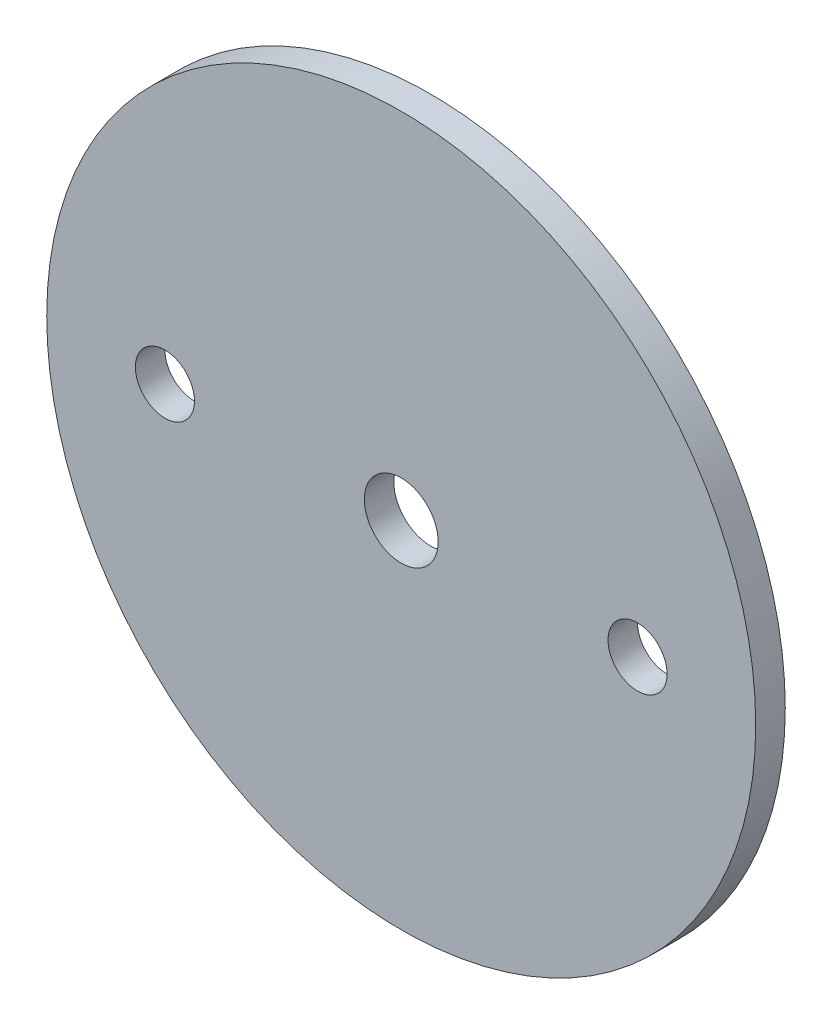
SolidWorks part; units mm, degrees
ref_plane "Front Plane" through (0, 0, 0) normal (0, 0, 1) x (1, 0, 0)
ref_plane "Top Plane" through (0, 0, 0) normal (0, 1, 0) x (1, 0, 0)
ref_plane "Right Plane" through (0, 0, 0) normal (1, 0, 0) x (0, 0, -1)
sketch "Sketch1" plane through (0, 0, 0) normal (0, 0, 1) x (1, 0, 0)
  circle A0 centre (0, 0) radius 38.1
extrude "Boss-Extrude1" add sketch "Sketch1" along normal mid plane 3.175
sketch "Sketch2" plane through (0, 0, 1.5875) normal (0, 0, 1) x (1, 0, 0)
  line L0 (-1000, 0) -> (49000, 0) construction
  line L1 (0, -1000) -> (0, 49000) construction
  point P4 (25.4, 0)
  point P5 (-25.4, 0)
  dimension "D2" = 50.8
  dimension "D1" = 25.4
hole_wizard "1/4 (0.25) Diameter Hole1" positions "Sketch2" profile "Sketch3" hole size "1/4" standard "ANSI Inch" end condition through all
sketch "Sketch3" plane through (-25.4, 0, 1.5875) normal (1, 0, 0) x (0, -1, 0)
  line L0 (0, 0) -> (0, 3.175)
  line L1 (0, 3.175) -> (3.175, 3.175)
  line L2 (3.175, 3.175) -> (3.175, 0)
  line L5 (3.175, 0) -> (0, 0)
  line L11 (0, -6.35) -> (0, 107.95) construction
  dimension "Thru Hole Dia." = 6.35
  dimension "Thru Hole Depth" = 3.175
sketch "Sketch4" plane through (0, 0, 1.5875) normal (0, 0, 1) x (1, 0, 0)
  point P0 (0, 0)
hole_wizard "5/16 (0.3125) Diameter Hole1" positions "Sketch4" profile "Sketch5" hole size "5/16" standard "ANSI Inch"
sketch "Sketch5" plane through (0, 0, 1.5875) normal (1, 0, 0) x (0, -1, 0)
  line L0 (0, 0) -> (0, 3.302)
  line L1 (0, 3.302) -> (3.9687, 3.302)
  line L2 (3.9687, 3.302) -> (3.9688, 0)
  line L5 (3.9688, 0) -> (0, 0)
  line L10 (0, 3.302) -> (-3.9688, 3.302) construction
  line L11 (0, -6.35) -> (0, 107.95) construction
  dimension "Hole Dia." = 7.9375
  dimension "Hole Depth" = 3.302
  dimension "Drill Angle" = 180
equation "\"AIRFRAME_OD\"= 3.091in"
equation "\"AIRFRAME_ID\"= 3.00in"
equation "\"FLAT_T\"= 0.125in"
equation "\"NOSE_EXP_L\"= 3.5in"
equation "\"NOSE_SHOULDER_L\"= 5in"
equation "\"MAIN_L\"= 30in"
equation "\"RECO_COUP_L\"= 6in"
equation "\"RECO_SWITCH_L\"= 1.5in"
equation "\"DROGUE_L\"= 14in"
equation "\"ATS_FORE_COUP_L\"= 4in"
equation "\"ATS_AFT_COUP_L\"= 2.5in"
equation "\"LOWER_L\"= 16in"
equation "\"FIN_N\"= 4"
equation "\"CR_AFT_X\"= 0.5in"
equation "\"CR_FORE_X\"= 6in"
equation "\"FIN_ROOT\"= 5in"
equation "\"FIN_X\"= 0.75in"
equation "\"MOTOR_OD\"= 2.25in"
equation "\"MOTOR_ID\"= 2.126in"
equation "\"COUPLER_OD\"= 2.998in"
equation "\"COUPLER_ID\"= 2.875in"
equation "\"D1@Sketch1\"=\"AIRFRAME_ID\""
equation "\"D1@Boss-Extrude1\"=\"FLAT_T\""
equation "\"RECO_ROD_X\"= 1.5in"
equation "\"ATS_ROD_X\"= 2in"
equation "\"D2@Sketch2\"=\"ATS_ROD_X\""
